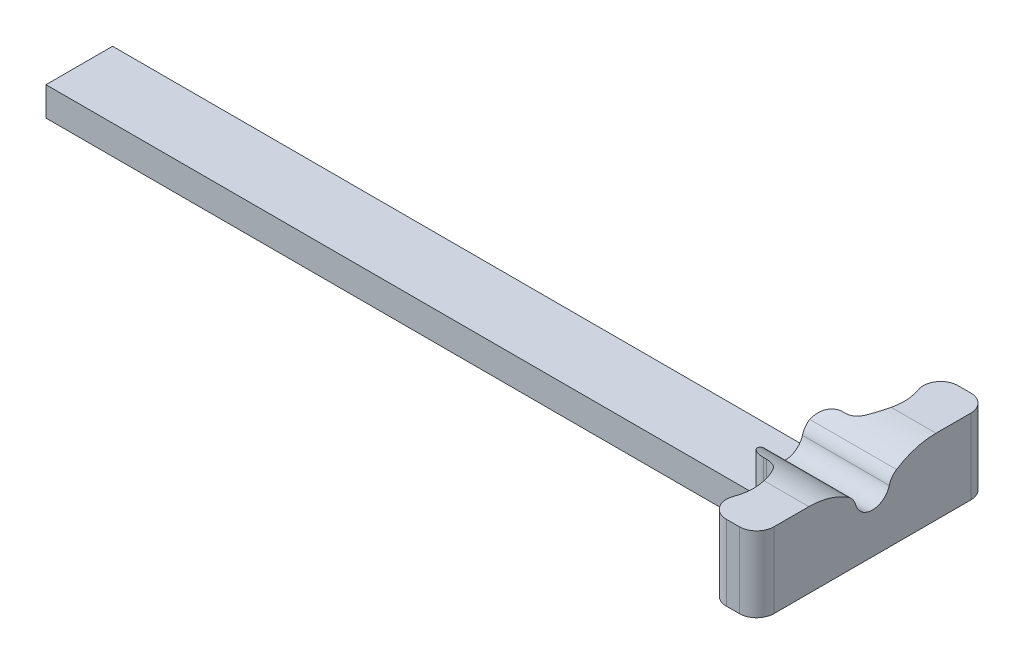
SolidWorks part; units mm, degrees
ref_plane "前视基准面" through (0, 0, 0) normal (0, 0, 1) x (1, 0, 0)
ref_plane "上视基准面" through (0, 0, 0) normal (0, 1, 0) x (1, 0, 0)
ref_plane "右视基准面" through (0, 0, 0) normal (1, 0, 0) x (0, 0, -1)
other "Configuration Table"
sketch "草图1" plane through (0, 0, 0) normal (0, 1, 0) x (1, 0, 0)
  line L0 (0, 0) -> (137, 0) construction
  line L1 (137, -17) -> (137, 17)
  line L2 (134, 20) -> (131.7819, 20)
  line L3 (125.5, 6.8377) -> (125, 6.8377)
  line L4 (122, 3.8377) -> (122, -3.8377)
  line L5 (0, -5.75) -> (0, 5.75)
  line L6 (0, 5.75) -> (122.6885, 5.75)
  line L7 (0, -5.75) -> (122.6885, -5.75)
  line L8 (125.5, -6.8377) -> (125, -6.8377)
  line L9 (134, -20) -> (131.7819, -20)
  arc A0 (128.9693, 15.9565) -> (127.9545, 8.1128) centre (121, 13) cw
  arc A1 (137, 17) -> (134, 20) centre (134, 17) ccw
  arc A2 (131.7819, 20) -> (128.9693, 15.9565) centre (131.7819, 17) ccw
  arc A3 (127.9545, 8.1128) -> (125.5, 6.8377) centre (125.5, 9.8377) cw
  arc A4 (125, 6.8377) -> (122, 3.8377) centre (125, 3.8377) ccw
  arc A5 (125, -6.8377) -> (122, -3.8377) centre (125, -3.8377) cw
  arc A6 (127.9545, -8.1128) -> (125.5, -6.8377) centre (125.5, -9.8377) ccw
  arc A7 (131.7819, -20) -> (128.9693, -15.9565) centre (131.7819, -17) cw
  arc A8 (137, -17) -> (134, -20) centre (134, -17) cw
  arc A9 (128.9693, -15.9565) -> (127.9545, -8.1128) centre (121, -13) ccw
  point P34 (122, 0)
  dimension "D3" = 8.5
  dimension "D6" = 3
  dimension "D1" = 137
  dimension "D2" = 40
  dimension "D4" = 26
  dimension "D5" = 16
  dimension "D7" = 11.5
  dimension "D8" = 122
  dimension "D9" = 11.5
extrude "凸台-拉伸1" add sketch "草图1" along normal blind 13 contours L4 L0 L1 A1 L2 A2 A0 A3 L3 A4 | L0 L4 A5 L8 A6 A9 A7 L9 A8 L1 region at (131.2857, 0, -8.286) region at (131.2857, 0, 8.286)
extrude "凸台-拉伸2" add sketch "草图1<3>" along normal blind 5 contours L5 L0 L4 A4 L6 | L0 L5 L7 A5 L4 region at (61.0363, 0, -2.8764) region at (61.0363, 0, 2.8764)
sketch "草图1<3>" plane through (0, 0, 0) normal (0, 1, 0) x (1, 0, 0) same geometry as "草图1"
sketch "草图2" plane through (137, 0, 0) normal (1, 0, 0) x (0, 0, -1)
  line L0 (0, 0) -> (0, 7) construction
  line L1 (-17, 0) -> (17, 0) construction
  line L2 (-17, 13) -> (17, 13) construction
  line L3 (-10.9796, 13) -> (10.9796, 13)
  arc A0 (-2.9, 9.2319) -> (2.9, 9.2319) centre (0, 10) ccw
  arc A1 (-2.9, 9.2319) -> (-4.1643, 10.9786) centre (-5.8, 8.4638) ccw
  arc A2 (-4.1643, 10.9786) -> (-10.9796, 13) centre (-10.9796, 0.5) ccw
  arc A3 (4.1643, 10.9786) -> (10.9796, 13) centre (10.9796, 0.5) cw
  arc A4 (2.9, 9.2319) -> (4.1643, 10.9786) centre (5.8, 8.4638) cw
  point P16 (0, 13)
  dimension "D1" = 6
  dimension "D3" = 3
  dimension "D5" = 12.5
  dimension "D2" = 10
  dimension "D4" = 11.6
extrude "切除-拉伸1" cut sketch "草图2" against normal through all
